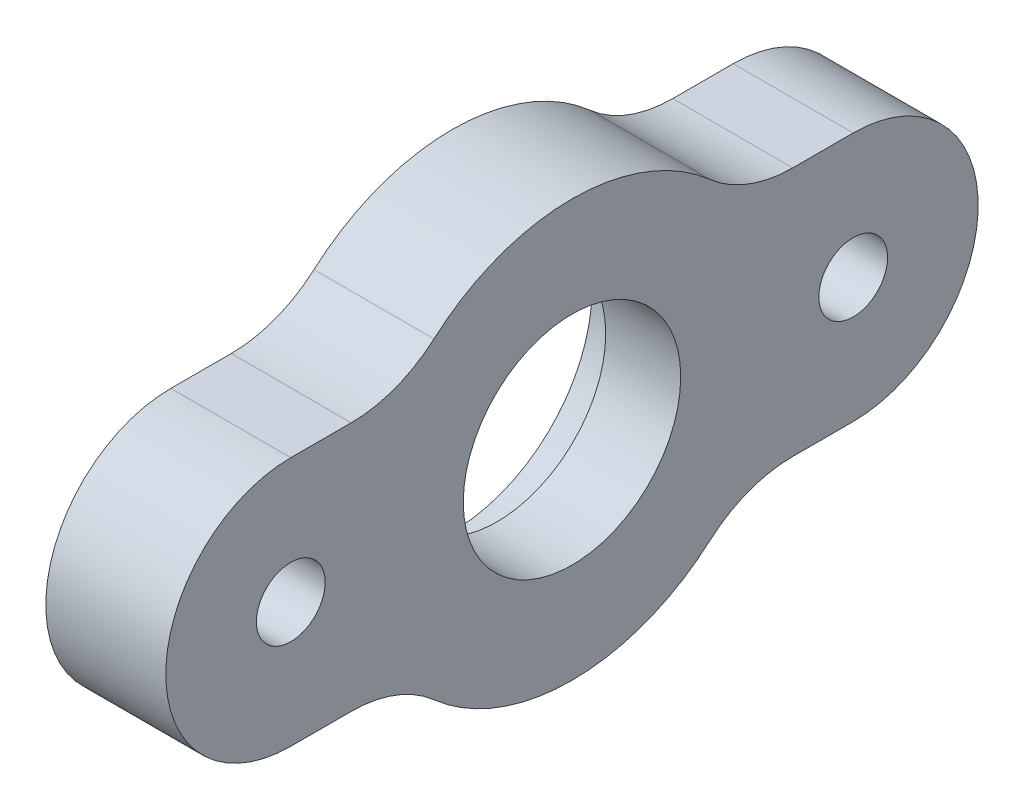
SolidWorks part; units mm, degrees
ref_plane "Ebene vorne" through (0, 0, 0) normal (0, 0, 1) x (1, 0, 0)
ref_plane "Ebene oben" through (0, 0, 0) normal (0, 1, 0) x (1, 0, 0)
ref_plane "Ebene rechts" through (0, 0, 0) normal (1, 0, 0) x (0, 0, -1)
sketch "Skizze4" plane through (0, 0, 0) normal (0, 0, 1) x (1, 0, 0)
  line L0 (0, 11.2) -> (3.6, 11.2)
  line L1 (0, 11.2) -> (0, 16.6831)
  line L2 (0, 16.6831) -> (9.6, 16.6831)
  line L3 (9.6, 16.6831) -> (9.6, 8.7)
  line L4 (9.6, 8.7) -> (3.6, 8.7)
  line L5 (3.6, 8.7) -> (3.6, 11.2)
  line L6 (0, 0) -> (13.1594, 0) construction
  dimension "D1" = 11.2
  dimension "D2" = 3.6
  dimension "D3" = 2.5
  dimension "D4" = 6
revolve "Rotation1" add sketch "Skizze4" angle 360 about L6
sketch "Skizze5" plane through (9.6, 0, 0) normal (1, 0, 0) x (0, 0, -1)
  line L0 (-22.5, 0) -> (22.5, 0) construction
  line L1 (-22.5, 0) -> (22.5, 0) construction
  line L2 (-22.5, 10) -> (-13.3538, 10)
  line L3 (-22.5, -10) -> (-13.3538, -10)
  arc A3 (-22.5, 10) -> (-22.5, -10) centre (-22.5, 0) ccw
  arc A5 (-13.3538, 10) -> (-13.3538, -10) centre (0, 0) ccw
  circle A6 centre (0, 0) radius 16.6831 construction
  arc A7 (13.3538, 10) -> (13.3538, -10) centre (0, 0) ccw
  point P0 (0, 0)
  point P4 (0, 0)
  point P16 (-22.5, 0)
  dimension "D2" = 20
  dimension "D1" = 45
extrude "Aufsatz-Linear austragen1" add sketch "Skizze5" against normal blind 9.6 contours L3 A5 L2 A3
hole_wizard "Ø5.5 (5.5) Durchmesser Bohrung1" positions "Skizze6" profile "Skizze7" hole size "Ø5.5" standard "ISO" end condition through all
sketch "Skizze6" plane through (9.6, 0, 0) normal (1, 0, 0) x (0, 0, -1)
  point P0 (-22.5, 0)
sketch "Skizze7" plane through (9.6, 0, 22.5) normal (0, 1, 0) x (0, 0, -1)
  line L0 (0, 0) -> (0, 9.6)
  line L1 (0, 9.6) -> (2.75, 9.6)
  line L2 (2.75, 9.6) -> (2.75, 0)
  line L5 (2.75, 0) -> (0, 0)
  line L11 (0, -6.35) -> (0, 107.95) construction
  dimension "Bohrerdurchmesser" = 5.5
  dimension "Bohrungstiefe" = 9.6
mirror "Spiegeln1" about plane through (0, 0, 0) normal (0, 0, 1) of "Ø5.5 (5.5) Durchmesser Bohrung1", "Aufsatz-Linear austragen1"
fillet "Verrundung2" radius 10 4 edges at (4.8, -10, 13.3538) (4.8, 10, 13.3538) (4.8, -10, -13.3538) (4.8, 10, -13.3538)
